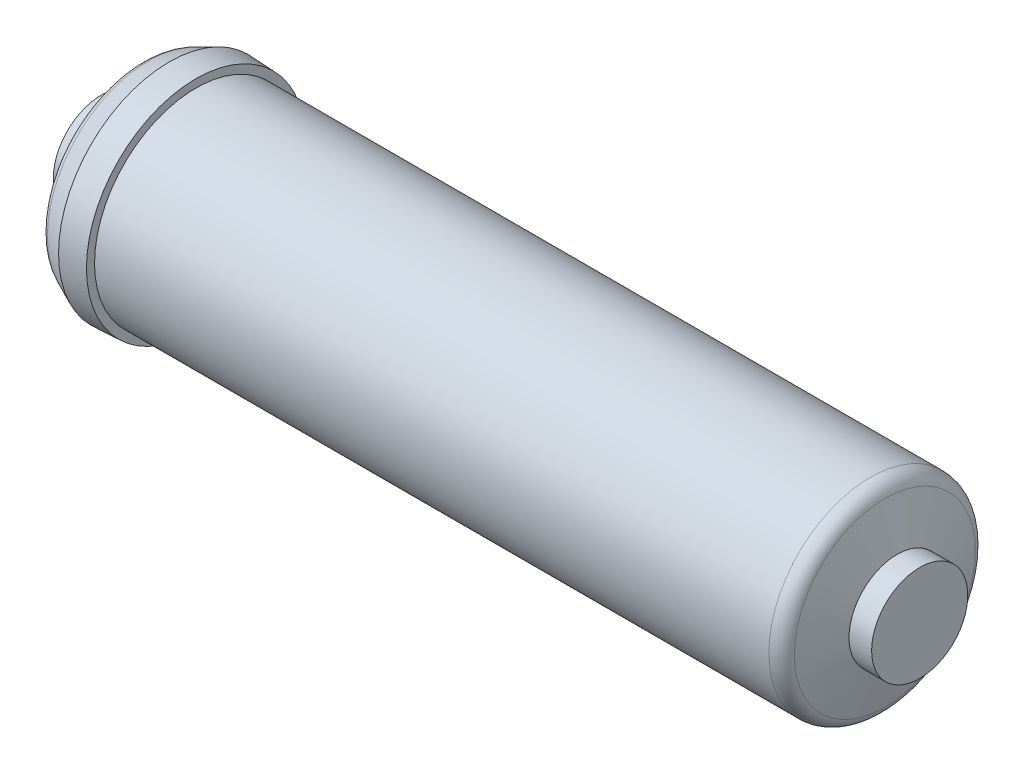
SolidWorks part; units mm, degrees
ref_plane "Front Plane" through (0, 0, 0) normal (0, 0, 1) x (1, 0, 0)
ref_plane "Top Plane" through (0, 0, 0) normal (0, 1, 0) x (1, 0, 0)
ref_plane "Right Plane" through (0, 0, 0) normal (1, 0, 0) x (0, 0, -1)
sketch "Sketch1" plane through (0, 0, 0) normal (0, 0, 1) x (1, 0, 0)
  line L1 (257.175, 0) -> (257.175, 15.113)
  line L2 (257.175, 15.113) -> (250.063, 15.113)
  line L3 (250.063, 15.113) -> (245.237, 31.877)
  line L4 (245.237, 31.877) -> (29.718, 31.877)
  line L5 (29.718, 31.877) -> (29.718, 34.417)
  line L6 (29.718, 34.417) -> (21.336, 34.798)
  line L7 (21.336, 34.798) -> (12.954, 30.988)
  line L8 (12.954, 30.988) -> (7.9502, 15.113)
  line L9 (7.9502, 15.113) -> (0, 15.113)
  line L10 (0, 15.113) -> (0, 0)
  line L11 (0, 0) -> (257.175, 0) construction
  line L12 (0, 0) -> (257.175, 0)
  dimension "D1" = 257.175
  dimension "D2" = 30.226
  dimension "D3" = 7.9502
  dimension "D4" = 7.112
  dimension "D5" = 69.596
  dimension "D6" = 29.718
  dimension "D7" = 63.754
  dimension "D8" = 2.54
  dimension "D9" = 8.382
  dimension "D10" = 8.382
  dimension "D11" = 61.976
  dimension "D12" = 11.938
revolve "Revolve1" add sketch "Sketch1" angle 360 about L11
fillet "Fillet1" radius 4.7625 2 edges at (12.954, 0, 30.988) (245.237, 0, 31.877)
shell "Shell1" thickness 2.54 removed face at (0, 0, 15.113)
